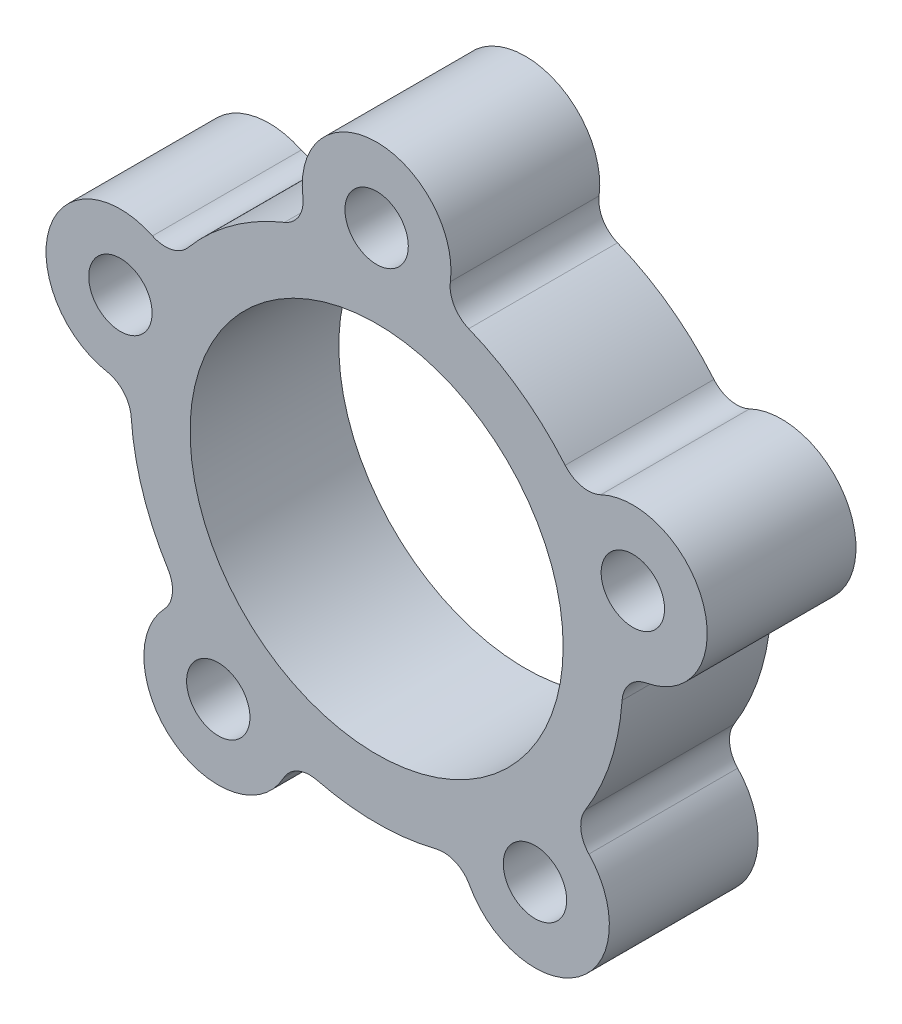
SolidWorks part; units mm, degrees
material "6061-T6 (SS)"
ref_plane "Front Plane" through (0, 0, 0) normal (0, 0, 1) x (1, 0, 0)
ref_plane "Top Plane" through (0, 0, 0) normal (0, 1, 0) x (1, 0, 0)
ref_plane "Right Plane" through (0, 0, 0) normal (1, 0, 0) x (0, 0, -1)
sketch "Sketch1" plane through (0, 0, 11.1125) normal (0, 0, 1) x (1, 0, 0)
  circle A1 centre (0, 0) radius 7.9629
  circle A2 centre (0, 0) radius 7.9629
  arc A10 (8.0479, 6.7485) -> (3.9313, 9.7394) centre (0, 0) ccw
  arc A11 (3.1476, 11.0836) -> (-3.1476, 11.0836) centre (0, 11.5) ccw
  arc A12 (-3.9313, 9.7394) -> (-8.0479, 6.7485) centre (0, 0) ccw
  arc A13 (-9.5685, 6.4186) -> (-11.5138, 0.4315) centre (-10.9371, 3.5537) ccw
  arc A14 (-10.4776, -0.7292) -> (-8.9051, -5.5686) centre (0, 0) ccw
  arc A15 (-9.0612, -7.1167) -> (-3.9684, -10.817) centre (-6.7595, -9.3037) ccw
  arc A16 (-2.5442, -10.1901) -> (2.5442, -10.1901) centre (0, 0) ccw
  arc A17 (3.9684, -10.817) -> (9.0612, -7.1167) centre (6.7595, -9.3037) ccw
  arc A18 (8.9051, -5.5686) -> (10.4776, -0.7292) centre (0, 0) ccw
  arc A19 (11.5138, 0.4315) -> (9.5685, 6.4186) centre (10.9371, 3.5537) ccw
  arc A20 (8.0479, 6.7485) -> (3.9313, 9.7394) centre (0, 0) ccw
  arc A21 (3.1476, 11.0836) -> (-3.1476, 11.0836) centre (0, 11.5) ccw
  arc A22 (-3.9313, 9.7394) -> (-8.0479, 6.7485) centre (0, 0) ccw
  arc A23 (-9.5685, 6.4186) -> (-11.5138, 0.4315) centre (-10.9371, 3.5537) ccw
  arc A24 (-10.4776, -0.7292) -> (-8.9051, -5.5686) centre (0, 0) ccw
  arc A25 (-9.0612, -7.1167) -> (-3.9684, -10.817) centre (-6.7595, -9.3037) ccw
  arc A26 (-2.5442, -10.1901) -> (2.5442, -10.1901) centre (0, 0) ccw
  arc A27 (3.9684, -10.817) -> (9.0612, -7.1167) centre (6.7595, -9.3037) ccw
  arc A28 (8.9051, -5.5686) -> (10.4776, -0.7292) centre (0, 0) ccw
  arc A29 (11.5138, 0.4315) -> (9.5685, 6.4186) centre (10.9371, 3.5537) ccw
  arc A72 (8.0479, 6.7485) -> (9.5685, 6.4186) centre (9.0211, 7.5645) ccw
  arc A73 (8.0479, 6.7485) -> (9.5685, 6.4186) centre (9.0211, 7.5645) ccw
  arc A74 (3.1476, 11.0836) -> (3.9313, 9.7394) centre (4.4066, 10.9171) ccw
  arc A75 (3.1476, 11.0836) -> (3.9313, 9.7394) centre (4.4066, 10.9171) ccw
  arc A76 (-3.9313, 9.7394) -> (-3.1476, 11.0836) centre (-4.4066, 10.9171) ccw
  arc A77 (-3.9313, 9.7394) -> (-3.1476, 11.0836) centre (-4.4066, 10.9171) ccw
  arc A78 (-9.5685, 6.4186) -> (-8.0479, 6.7485) centre (-9.0211, 7.5645) ccw
  arc A79 (-9.5685, 6.4186) -> (-8.0479, 6.7485) centre (-9.0211, 7.5645) ccw
  arc A80 (-10.4776, -0.7292) -> (-11.5138, 0.4315) centre (-11.7445, -0.8174) ccw
  arc A81 (-10.4776, -0.7292) -> (-11.5138, 0.4315) centre (-11.7445, -0.8174) ccw
  arc A82 (-9.0612, -7.1167) -> (-8.9051, -5.5686) centre (-9.9819, -6.242) ccw
  arc A83 (-9.0612, -7.1167) -> (-8.9051, -5.5686) centre (-9.9819, -6.242) ccw
  arc A84 (-2.5442, -10.1901) -> (-3.9684, -10.817) centre (-2.8519, -11.4223) ccw
  arc A85 (-2.5442, -10.1901) -> (-3.9684, -10.817) centre (-2.8519, -11.4223) ccw
  arc A86 (3.9684, -10.817) -> (2.5442, -10.1901) centre (2.8519, -11.4223) ccw
  arc A87 (3.9684, -10.817) -> (2.5442, -10.1901) centre (2.8519, -11.4223) ccw
  arc A88 (8.9051, -5.5686) -> (9.0612, -7.1167) centre (9.9819, -6.242) ccw
  arc A89 (8.9051, -5.5686) -> (9.0612, -7.1167) centre (9.9819, -6.242) ccw
  arc A90 (11.5138, 0.4315) -> (10.4776, -0.7292) centre (11.7445, -0.8174) ccw
  arc A91 (11.5138, 0.4315) -> (10.4776, -0.7292) centre (11.7445, -0.8174) ccw
  dimension "D1" = 0
  dimension "D2" = 0
extrude "Boss-Extrude1" add sketch "Sketch1" along normal blind 6.35
sketch "Sketch4" plane through (0, 0, 17.4625) normal (0, 0, 1) x (1, 0, 0)
  point P0 (-10.9371, 3.5537)
  point P3 (0, 11.5)
  point P6 (10.9371, 3.5537)
  point P9 (6.7595, -9.3037)
  point P12 (-6.7595, -9.3037)
hole_wizard "#6-32 Tapped Hole1" positions "Sketch4" profile "Sketch3" tap size "#6-32" standard "ANSI Inch" end condition through all
sketch "Sketch3" plane through (-10.9371, 3.5537, 17.4625) normal (1, 0, 0) x (0, -1, 0)
  line L0 (0, 0) -> (0, 6.35)
  line L1 (0, 6.35) -> (1.3525, 6.35)
  line L2 (1.3525, 6.35) -> (1.3525, 0)
  line L5 (1.3525, 0) -> (0, 0)
  line L11 (0, -6.35) -> (0, 107.95) construction
  dimension "Thru Tap Drill Dia." = 2.7051
  dimension "Thru Tap Drill Depth" = 6.35
cosmetic thread "Hole Thread1" parameters "D2"=3.5052
cosmetic thread "Hole Thread2" parameters "D2"=3.5052
cosmetic thread "Hole Thread3" parameters "D2"=3.5052
cosmetic thread "Hole Thread4" parameters "D2"=3.5052
cosmetic thread "Hole Thread5" parameters "D2"=3.5052
